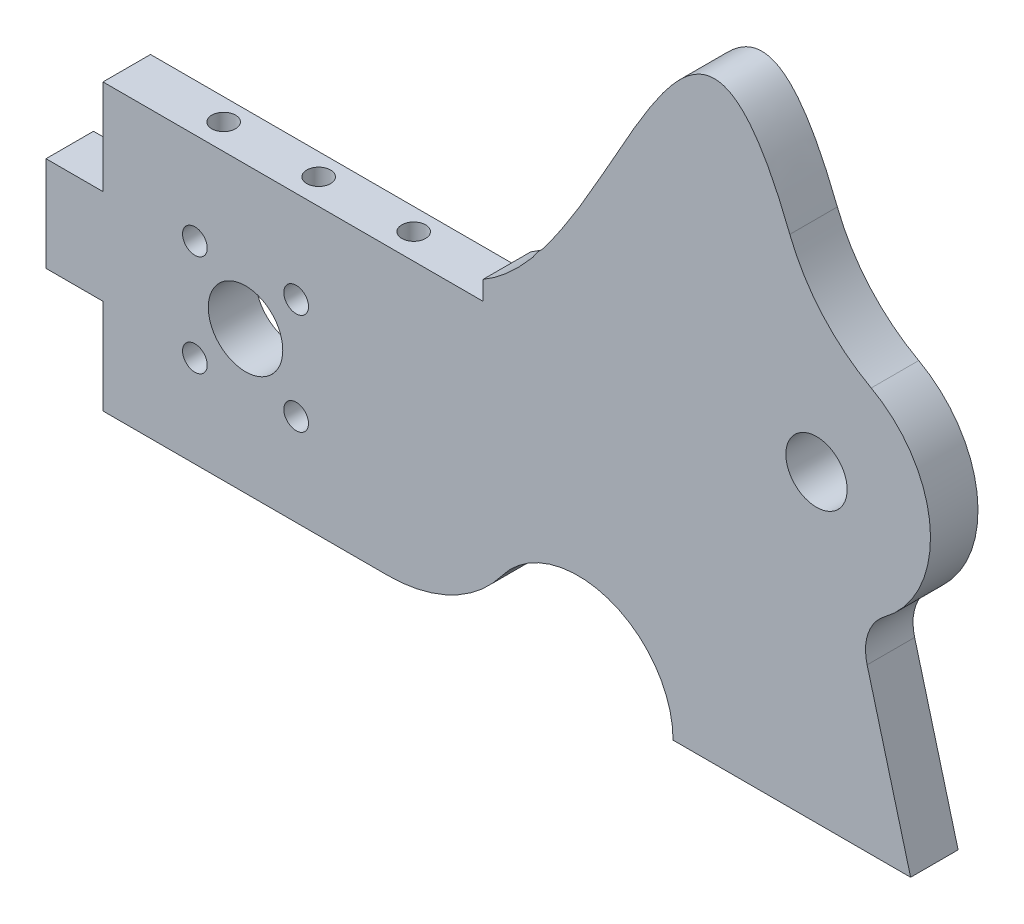
SolidWorks part; units mm, degrees
ref_plane "Front Plane" through (0, 0, 0) normal (0, 0, 1) x (1, 0, 0)
ref_plane "Top Plane" through (0, 0, 0) normal (0, 1, 0) x (1, 0, 0)
ref_plane "Right Plane" through (0, 0, 0) normal (1, 0, 0) x (0, 0, -1)
sketch "Sketch1" plane through (0, 0, 0) normal (0, 0, 1) x (1, 0, 0)
  line L0 (0, 0) -> (107.95, 0)
  line L3 (0, 38.1) -> (0, 25.4)
  line L4 (95.3675, 55.88) -> (0, 38.1)
  line L5 (0, 19.05) -> (100.2273, 19.05) construction
  line L6 (19.05, 19.05) -> (19.05, 28.62) construction
  line L7 (19.05, 19.05) -> (25.817, 25.817) construction
  line L8 (107.95, 0) -> (100.9363, 26.1756)
  line L10 (0, 12.7) -> (0, 0)
  line L11 (0, 25.4) -> (-7.62, 25.4)
  line L13 (0, 12.7) -> (-7.62, 12.7)
  line L14 (-7.62, 25.4) -> (-7.62, 12.7)
  line L15 (100.9363, 26.1756) -> (100.8688, 26.4276)
  arc A0 (100.8688, 26.4276) -> (95.3675, 55.88) centre (95.3675, 40.64) ccw
  circle A1 centre (95.3675, 40.64) radius 4.0957
  circle A2 centre (19.05, 19.05) radius 9.57 construction
  circle A3 centre (25.817, 25.817) radius 1.651
  circle A4 centre (25.817, 12.283) radius 1.651
  circle A5 centre (12.283, 12.283) radius 1.651
  circle A6 centre (12.283, 25.817) radius 1.651
  point P26 (19.05, 19.05)
  dimension "D1" = 8.1915
  dimension "D5" = 15.24
  dimension "D4" = 19.14
  dimension "D7" = 3.302
  dimension "D11" = 97.0107
  dimension "D2" = 38.1
  dimension "D3" = 40.64
  dimension "D6" = 107.95
  dimension "D8" = 45
  dimension "D9" = 4
  dimension "D10" = 19.05
  dimension "D12" = 75
  dimension "D14" = 12.7
  dimension "D15" = 12.7
  dimension "D16" = 7.62
extrude "Boss-Extrude1" add sketch "Sketch1" along normal blind 6.35
sketch "Sketch2" plane through (0, 0, 6.35) normal (0, 0, 1) x (1, 0, 0)
  circle A0 centre (95.3675, 40.64) radius 38.1 construction
sketch "Sketch3" plane through (0, 0, 0) normal (-1, 0, 0) x (0, 0, 1)
  line L0 (0, 38.1) -> (6.35, 25.4) construction
  line L1 (6.35, 12.7) -> (0, 0) construction
  circle A0 centre (3.175, 31.75) radius 1.5875
  circle A1 centre (3.175, 6.35) radius 1.5875
  dimension "D1" = 3.175
  dimension "D2" = 3.175
extrude "Cut-Extrude1" cut sketch "Sketch3" against normal blind 6.35
sketch "Sketch6" plane through (0, 0, 6.35) normal (0, 0, 1) x (1, 0, 0)
  line L0 (0, 0) -> (107.95, 0) construction
  line L1 (50.8, 0) -> (76.2, 0)
  arc A0 (76.2, 0) -> (50.8, 0) centre (63.5, 0) ccw
  dimension "D1" = 25.4
  dimension "D2" = 31.75
extrude "Cut-Extrude2" cut sketch "Sketch6" against normal blind 6.35
sketch "Sketch7" plane through (0, 0, 6.35) normal (0, 0, 1) x (1, 0, 0)
  line L0 (12.283, 25.817) -> (25.817, 12.283) construction
  line L1 (12.283, 12.283) -> (25.817, 25.817) construction
  circle A0 centre (19.05, 19.05) radius 4.9784
  dimension "D1" = 9.9568
extrude "Cut-Extrude3" cut sketch "Sketch7" against normal through all
fillet "Fillet1" radius 6.35 1 edges at (100.8688, 26.4276, 3.175)
sketch "Sketch8" plane through (0, 0, 6.35) normal (0, 0, 1) x (1, 0, 0)
  line L1 (0, 38.1) -> (50.8, 38.1)
  line L2 (0, 38.1) -> (0, 50.8)
  line L3 (0, 50.8) -> (50.8, 50.8)
  line L4 (50.8, 38.1) -> (50.8, 50.8)
  dimension "D1" = 50.8
  dimension "D2" = 12.7
extrude "Cut-Extrude4" cut sketch "Sketch8" against normal blind 50.8
sketch "Sketch9" plane through (0, 0, 6.35) normal (0, 0, 1) x (1, 0, 0)
  line L3 (50.8, 40.64) -> (57.15, 40.64)
  line L5 (57.15, 40.64) -> (50.8, 40.64)
  line L6 (57.15, 40.64) -> (57.15, 50.8)
  line L7 (57.15, 50.8) -> (50.8, 50.8)
  line L8 (50.8, 40.64) -> (50.8, 50.8)
  line L9 (0, 38.1) -> (50.8, 38.1) construction
  line M8 (50.8, 47.571) -> (50.8, 38.1)
  line M21 (95.3675, 55.88) -> (50.8, 47.571)
  dimension "D1" = 10.16
  dimension "D2" = 2.54
  dimension "D3" = 6.35
extrude "Cut-Extrude5" cut sketch "Sketch9" against normal blind 19.304 contours L3 L6 M21 M8 region at (54.0583, 44.4092, 6.35)
fillet "Fillet6" radius 6.35 1 edges at (57.15, 40.64, 3.175)
fillet "Fillet7" radius 6.35 1 edges at (57.15, 48.7549, 3.175)
fillet "Fillet8" radius 19.05 1 edges at (50.8, 0, 3.175)
sketch "Sketch10" plane through (0, 0, 0) normal (0, -1, 0) x (1, 0, 0)
  line L0 (76.2, 6.35) -> (107.95, 6.35) construction
  line L1 (0, 6.35) -> (0, 0) construction
  line L2 (0, 6.35) -> (38.1, 6.35) construction
  line L3 (107.95, 6.35) -> (107.95, 0) construction
  line L4 (76.2, 0) -> (76.2, 6.35) construction
  circle A0 centre (97.79, 3.175) radius 1.5875
  circle A1 centre (86.36, 3.175) radius 1.5875
  circle A2 centre (31.75, 3.175) radius 1.5875
  circle A3 centre (12.7, 3.175) radius 1.5875
  dimension "D1" = 3.175
  dimension "D2" = 3.175
  dimension "D3" = 3.175
  dimension "D4" = 3.175
  dimension "D5" = 12.7
  dimension "D6" = 19.05
  dimension "D7" = 10.16
  dimension "D8" = 10.16
  dimension "D9" = 11.43
  dimension "D10" = 3.175
  dimension "D11" = 3.175
extrude "Cut-Extrude6" cut sketch "Sketch10" against normal blind 6.35
sketch "Sketch11" plane through (0, 38.1, 0) normal (0, 1, 0) x (1, 0, 0)
  line L0 (0, -6.35) -> (0, 0) construction
  line L1 (50.8, 0) -> (50.8, -6.35) construction
  line L2 (0, -6.35) -> (50.8, -6.35) construction
  circle A0 centre (12.7, -2.9224) radius 1.5875
  circle A1 centre (25.4, -2.9224) radius 1.5875
  circle A2 centre (38.1, -2.9224) radius 1.5875
  dimension "D1" = 3.175
  dimension "D2" = 3.175
  dimension "D3" = 3.175
  dimension "D4" = 12.7
  dimension "D5" = 12.7
  dimension "D6" = 12.7
  dimension "D7" = 12.7
  dimension "D8" = 3.4276
extrude "Cut-Extrude7" cut sketch "Sketch11" against normal blind 6.35
sketch "Sketch12" plane through (0, 0, 6.35) normal (0, 0, 1) x (1, 0, 0)
  line L0 (107.95, 0) -> (146.812, 0) construction
  line L1 (8.0257, 45.4128) -> (80.6683, 75.7903) construction
  line L2 (95.3675, 40.64) -> (80.6683, 75.7903) construction
  line L3 (80.6683, 75.7903) -> (79.4434, 78.7195) construction
  line L4 (50.8, 40.64) -> (85.0271, 40.64)
  line L5 (85.0271, 40.64) -> (95.3675, 55.88)
  arc A0 (61.8128, 49.6242) -> (56.8883, 45.1859) centre (62.9766, 43.3817) ccw construction
  circle A1 centre (19.05, 19.05) radius 28.575 construction
  circle A2 centre (95.3675, 40.64) radius 38.1 construction
  circle A3 centre (80.6683, 75.7903) radius 3.175 construction
  spline S0 degree 3 poles (50.8, 40.64) (70.7778, 52.1788) (78.5943, 111.5434) (95.3675, 55.88) knots 0 0 0 0 1 1 1 1
  dimension "D2" = 6.35
  dimension "D1" = 38.862
extrude "Boss-Extrude2" add sketch "Sketch12" against normal blind 6.35
fillet "Fillet9" radius 24.13 1 edges at (95.3675, 55.88, 3.175)
